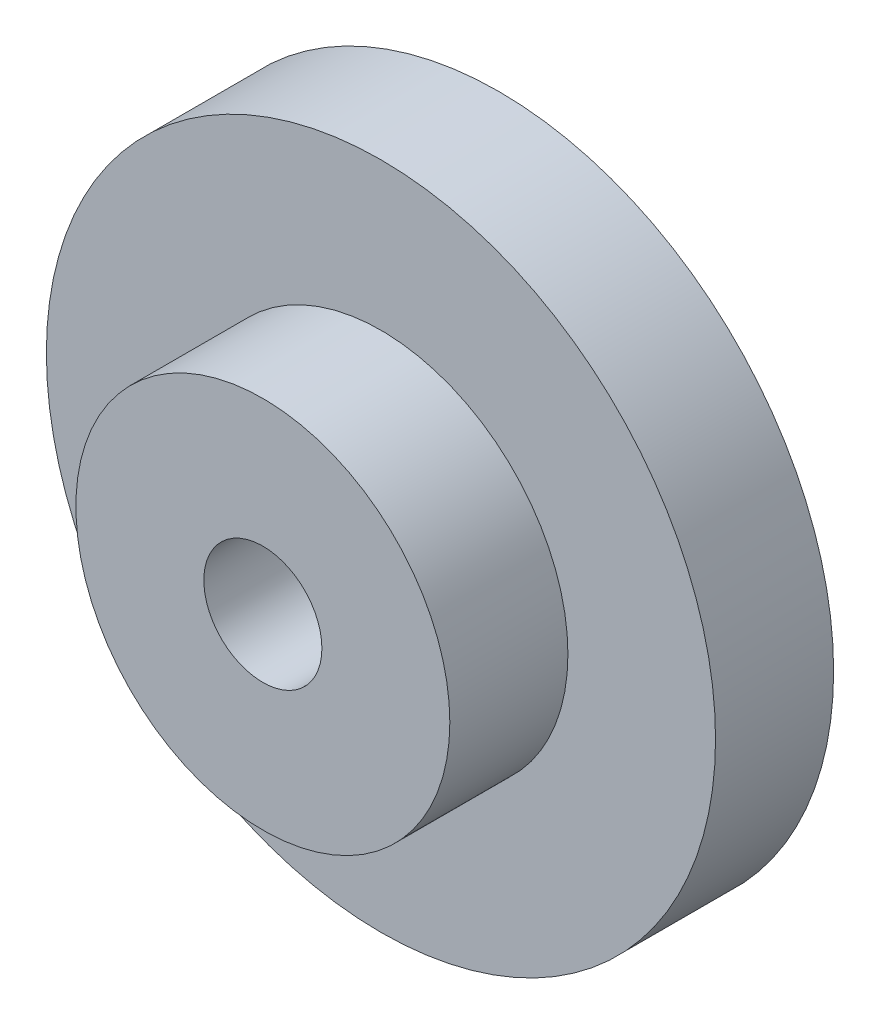
SolidWorks part; units mm, degrees
ref_plane "Front Plane" through (0, 0, 0) normal (0, 0, 1) x (1, 0, 0)
ref_plane "Top Plane" through (0, 0, 0) normal (0, 1, 0) x (1, 0, 0)
ref_plane "Right Plane" through (0, 0, 0) normal (1, 0, 0) x (0, 0, -1)
sketch "Sketch1" plane through (0, 0, 0) normal (1, 0, 0) x (0, 0, -1)
  line L0 (-3.3548, 0) -> (2.6452, 0)
  line L1 (2.6452, 0) -> (2.6452, 7)
  line L2 (2.6452, 7) -> (-0.3548, 7)
  line L3 (-0.3548, 7) -> (-0.3548, 3.25)
  line L4 (-0.3548, 3.25) -> (-3.3548, 3.25)
  line L5 (-3.3548, 3.25) -> (-3.3548, 0)
  line L6 (-3.3548, -1.5) -> (2.6452, -1.5) construction
  dimension "D1" = 3
  dimension "D2" = 1.5
  dimension "D3" = 4.75
  dimension "D4" = 3.75
revolve "Revolve1" add sketch "Sketch1" angle 360 about L6
